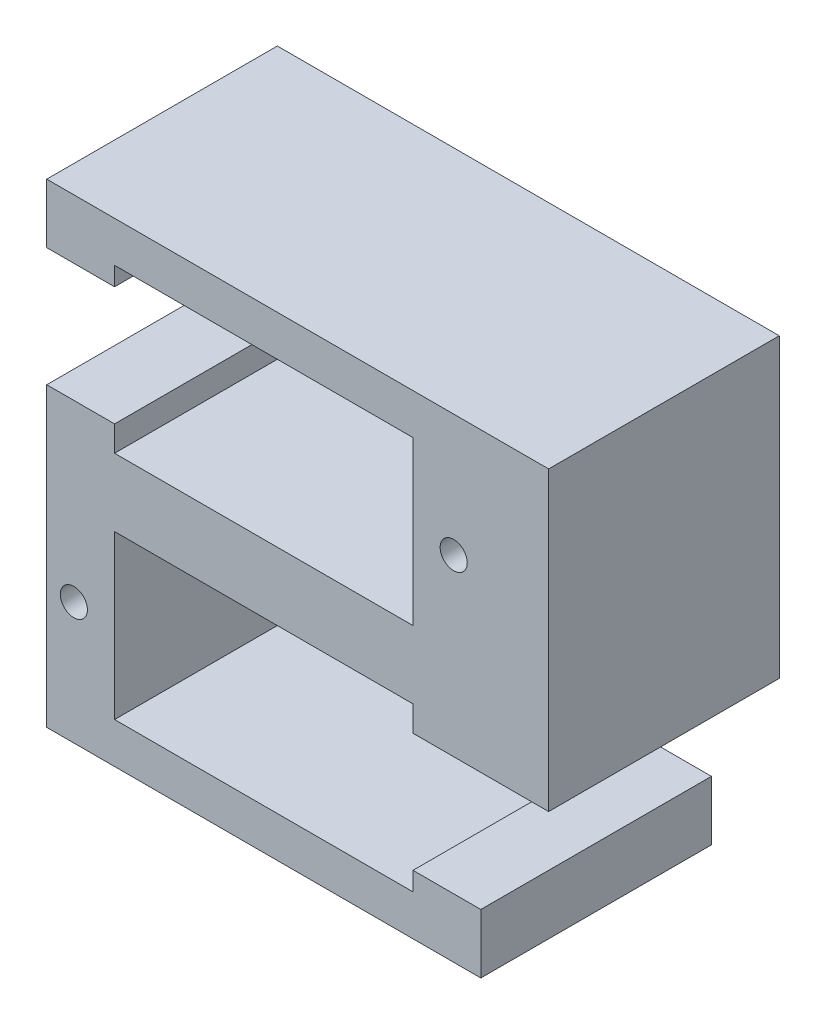
SolidWorks part; units mm, degrees
ref_plane "Front Plane" through (0, 0, 0) normal (0, 0, 1) x (1, 0, 0)
ref_plane "Top Plane" through (0, 0, 0) normal (0, 1, 0) x (1, 0, 0)
ref_plane "Right Plane" through (0, 0, 0) normal (1, 0, 0) x (0, 0, -1)
sketch "Sketch2" plane through (0, 0, 0) normal (0, 0, 1) x (1, 0, 0)
  line L0 (11.1122, 72.9799) -> (16.1122, 72.9799) construction
  line L1 (11.1122, 72.9799) -> (-10.8878, 72.9799)
  line L2 (11.1122, 72.9799) -> (11.1122, 43.9799)
  line L3 (11.1122, 43.9799) -> (-10.8878, 43.9799)
  line L4 (-10.8878, 72.9799) -> (-10.8878, 43.9799)
  line L5 (16.1122, 72.9799) -> (16.1122, 43.9799) construction
  line L6 (16.1122, 43.9799) -> (-15.8878, 43.9799) construction
  line L7 (-15.8878, 43.9799) -> (-15.8878, 72.9799) construction
  line L8 (-15.8878, 72.9799) -> (11.1122, 72.9799) construction
  line L9 (11.1122, 72.9799) -> (11.1122, 75.9799) construction
  line L10 (11.1122, 43.9799) -> (11.1122, 40.9799) construction
  line L11 (16.1122, 75.9799) -> (-15.8878, 75.9799)
  line L12 (16.1122, 75.9799) -> (16.1122, 40.9799)
  line L13 (16.1122, 40.9799) -> (-15.8878, 40.9799)
  line L14 (-15.8878, 75.9799) -> (-15.8878, 40.9799)
  line L15 (-10.8878, 60.9799) -> (11.1122, 60.9799)
  line L16 (11.1122, 55.9799) -> (-10.8878, 55.9799)
  dimension "D1" = 3
  dimension "D2" = 32
  dimension "D3" = 3
extrude "Boss-Extrude1" add sketch "Sketch2" against normal blind 35 contours L11 L14 L13 L12 L4 L1 L2 L3 | L16 L2 L15 L4 region at (0.1122, 58.4799, 0) region at (15.638, 58.4799, 0)
sketch "Sketch3" plane through (16.1122, 0, 0) normal (1, 0, 0) x (0, 0, -1)
  line L0 (35, 75.9799) -> (0, 75.9799) construction
  line L1 (15, 75.9799) -> (0, 75.9799)
  line L2 (15, 75.9799) -> (15, 40.9799)
  line L3 (15, 40.9799) -> (0, 40.9799)
  line L4 (0, 75.9799) -> (0, 40.9799)
  line L5 (0, 75.9799) -> (0, 40.9799) construction
  line L6 (15, 72.9799) -> (15, 75.9799) construction
extrude "Cut-Extrude1" cut sketch "Sketch3" against normal through all
sketch "Sketch4" plane through (-15.8878, 0, 0) normal (-1, 0, 0) x (0, 0, 1)
  line L0 (-35, 67.2299) -> (-35, 62.8549)
  line L1 (-35, 75.9799) -> (-35, 40.9799) construction
  line L2 (-35, 67.2299) -> (-35, 58.4799) construction
  line L3 (-35, 75.9799) -> (-35, 67.2299) construction
  line L4 (-35, 67.2299) -> (-35, 71.6049)
  line L5 (-15, 40.9799) -> (-15, 75.9799) construction
  line L6 (-15, 71.6049) -> (-35, 71.6049)
  line L7 (-15, 71.6049) -> (-15, 62.8549)
  line L8 (-15, 62.8549) -> (-35, 62.8549)
  line L9 (-35, 71.6049) -> (-35, 62.8549)
extrude "Cut-Extrude2" cut sketch "Sketch4" against normal up to next contours L7 L6 L9 L8
sketch "Sketch5" plane through (16.1122, 0, 0) normal (1, 0, 0) x (0, 0, -1)
  line L0 (35, 40.9799) -> (35, 58.4799) construction
  line L1 (35, 75.9799) -> (35, 40.9799) construction
  line L2 (35, 58.4799) -> (35, 49.7299) construction
  line L3 (35, 49.7299) -> (35, 40.9799) construction
  line L4 (35, 40.9799) -> (35, 45.3549) construction
  line L5 (35, 45.3549) -> (35, 54.1049) construction
  line L6 (15, 40.9799) -> (15, 75.9799) construction
  line L7 (35, 54.1049) -> (15, 54.1049)
  line L8 (35, 54.1049) -> (35, 45.3549)
  line L9 (35, 45.3549) -> (15, 45.3549)
  line L10 (15, 54.1049) -> (15, 45.3549)
extrude "Cut-Extrude3" cut sketch "Sketch5" against normal up to next
sketch "Sketch6" plane through (-15.8878, 0, 0) normal (-1, 0, 0) x (0, 0, 1)
  line L0 (-35, 40.9799) -> (-15, 40.9799) construction
  line L1 (-35, 75.9799) -> (-32, 75.9799)
  line L2 (-35, 75.9799) -> (-35, 40.9799)
  line L3 (-35, 40.9799) -> (-32, 40.9799)
  line L4 (-32, 75.9799) -> (-32, 40.9799)
  line L5 (-32, 72.9799) -> (-32, 60.9799) construction
extrude "Cut-Extrude4" cut sketch "Sketch6" against normal through all
sketch "Sketch7" plane through (16.1122, 0, 0) normal (1, 0, 0) x (0, 0, -1)
  line L1 (15, 75.9799) -> (32, 75.9799)
  line L2 (15, 75.9799) -> (15, 54.1049)
  line L3 (15, 54.1049) -> (32, 54.1049)
  line L4 (32, 75.9799) -> (32, 54.1049)
extrude "Boss-Extrude2" add sketch "Sketch7" along normal blind 5
sketch "Sketch8" plane through (16.1122, 0, 0) normal (1, 0, 0) x (0, 0, -1)
  line L0 (23.5, 75.9799) -> (23.5, 54.1049) construction
  line L1 (32, 75.9799) -> (15, 75.9799) construction
  line L2 (15, 54.1049) -> (32, 54.1049) construction
  line L3 (23.5, 65.0424) -> (32, 65.0424) construction
  line L5 (32, 54.1049) -> (32, 75.9799) construction
  circle A0 centre (23.5, 65.0424) radius 3
  dimension "D1" = 6
sketch "Sketch11" plane through (0, 0, -15) normal (0, 0, 1) x (1, 0, 0)
  circle A0 centre (14.1122, 66.9799) radius 1
  circle A1 centre (-13.8878, 49.9799) radius 1
  dimension "D1" = 2
  dimension "D2" = 2
extrude "Cut-Extrude5" cut sketch "Sketch11" against normal blind 10
ref_plane "Plane1" through (0, 0, -37) normal (0, 0, -1) x (-1, 0, 0)
